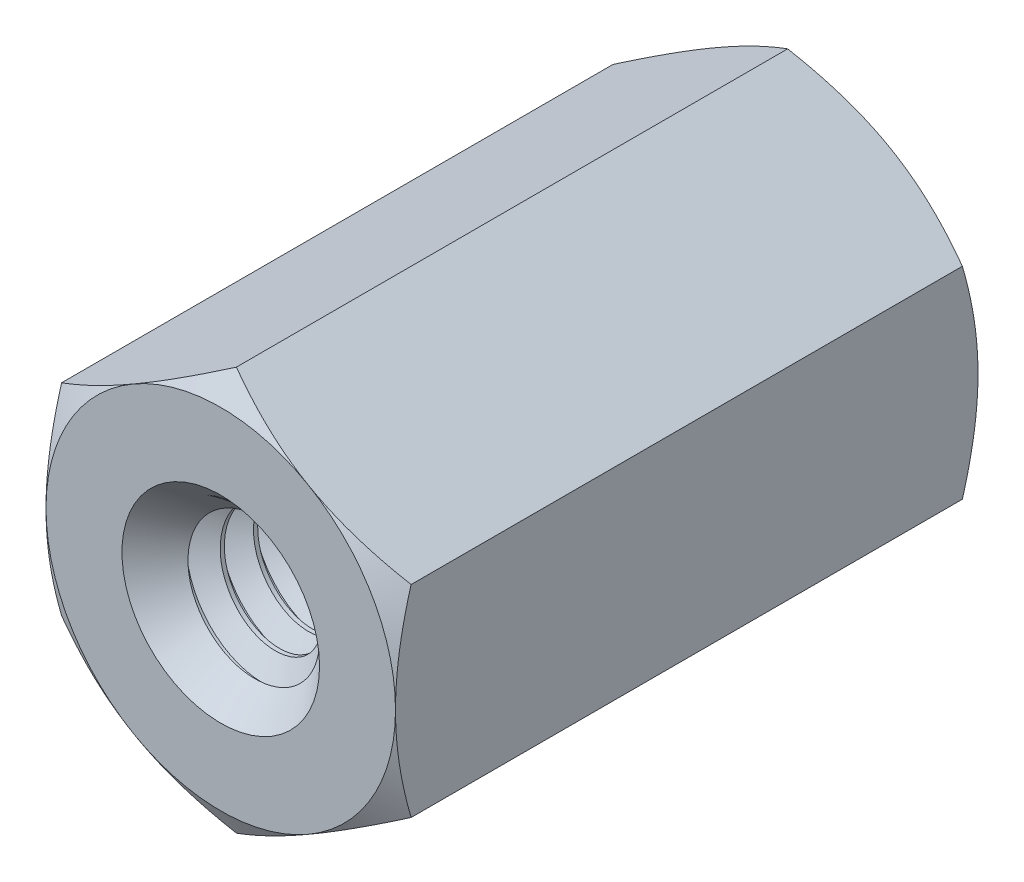
SolidWorks part; units mm, degrees
ref_plane "Front Plane" through (0, 0, 0) normal (0, 0, 1) x (1, 0, 0)
ref_plane "Top Plane" through (0, 0, 0) normal (0, 1, 0) x (1, 0, 0)
ref_plane "Right Plane" through (0, 0, 0) normal (1, 0, 0) x (0, 0, -1)
sketch "Sketch1" plane through (0, 0, 0) normal (0, 0, 1) x (1, 0, 0)
  line L1 (0, 2.7496) -> (-2.3813, 1.3748)
  line L2 (-2.3813, 1.3748) -> (-2.3813, -1.3748)
  line L3 (-2.3813, -1.3748) -> (0, -2.7496)
  line L4 (0, -2.7496) -> (2.3812, -1.3748)
  line L5 (2.3812, -1.3748) -> (2.3812, 1.3748)
  line L6 (2.3812, 1.3748) -> (0, 2.7496)
  circle A0 centre (0, 0) radius 2.3813 construction
  dimension "Hex" = 4.7625
extrude "Extrude1" add sketch "Sketch1" against normal blind 7.9375
sketch "Sketch2" plane through (0, 0, 0) normal (0, 0, 1) x (1, 0, 0)
  circle A0 centre (0, 0) radius 2.3813 construction
  circle A1 centre (0, 0) radius 2.3813
extrude "Cut-Extrude1" cut sketch "Sketch2" against normal through all draft 60 flip side to cut
sketch "Sketch3" plane through (0, 0, -7.9375) normal (0, 0, -1) x (-1, 0, 0)
  circle A1 centre (0, 0) radius 2.3813
  circle A2 centre (0, 0) radius 2.3813
  dimension "D1" = 0
extrude "Cut-Extrude2" cut sketch "Sketch3" against normal through all draft 60 flip side to cut
sketch "Sketch4" plane through (0, 0, 0) normal (0, 0, 1) x (1, 0, 0)
  circle A0 centre (0, 0) radius 1.0922
  dimension "Thread Dia" = 2.1844
extrude "Cut-Extrude3" cut sketch "Sketch4" against normal through all
sketch "Sketch7" plane through (0, 0, 0) normal (0, 0, 1) x (1, 0, 0)
  circle A4 centre (0, 0) radius 1.3462
  circle A5 centre (0, 0) radius 1.3462
  dimension "D1" = 0.254
sketch "Sketch8" plane through (0, 0, -7.9375) normal (0, 0, -1) x (-1, 0, 0)
  circle A1 centre (0, 0) radius 1.3462
  circle A2 centre (0, 0) radius 1.3462 construction
sketch "Sketch5" plane through (0, 0, 0) normal (0, 0, 1) x (1, 0, 0)
  circle A0 centre (0, 0) radius 1.0922 construction
  circle A1 centre (0, 0) radius 1.0922
curve "Helix/Spiral1" pitch 0.4536 height 8.3911 radius 1.0922 centre (0, 0, 0) axis (0, 0, -1) start towards (0, 1, 0) parameters "pitch"=0.4536
sketch "Sketch9" plane through (0, 0, 0) normal (1, 0, 0) x (0, 0, -1)
  line L0 (-0.2268, 1.0922) -> (-0.1701, 1.0922)
  line L1 (-0.1701, 1.0922) -> (0, 0.7976)
  line L2 (-0.2268, 1.0922) -> (-0.3969, 0.7976)
  line L3 (-0.3969, 0.7976) -> (0, 0.7976)
  line L4 (-0.1984, 1.0922) -> (-0.1984, 0.7976) construction
  line L5 (-0.3118, 0.9449) -> (-0.085, 0.9449) construction
  line L7 (0, 0.7976) -> (0, 1.0922) construction
  line L8 (0, 1.0922) -> (0, -1.0922) construction
  dimension "D1" = 0.0567
  dimension "D2" = 0.2268
  dimension "D3" = 60
sketch "Sketch12" plane through (0, 0, 0) normal (0, 0, 1) x (1, 0, 0)
  circle A0 centre (0, 0) radius 0.7976
  circle A1 centre (0, 0) radius 1.0922 construction
  circle A2 centre (0, 0) radius 1.0922
extrude "Extrude2" add sketch "Sketch12" against normal up to surface (7.9375 mm away) up to face at (1.0922, 0, -7.9375)
sweep "Cut-Sweep1" cut profiles "Sketch9" path "Helix/Spiral1" align with end faces yes
extrude "Cut-Extrude6" cut sketch "Sketch7" against normal through all draft 45
extrude "Cut-Extrude7" cut sketch "Sketch8" against normal through all draft 45
equation "\"D2@Sketch9\" = \"pitch@Helix/Spiral1\"*.5"
equation "\"D3@Helix/Spiral1\" = \"pitch@Helix/Spiral1\"+\"Height@Extrude1\""
equation "\"D1@Sketch9\" = \"pitch@Helix/Spiral1\"*.125"
